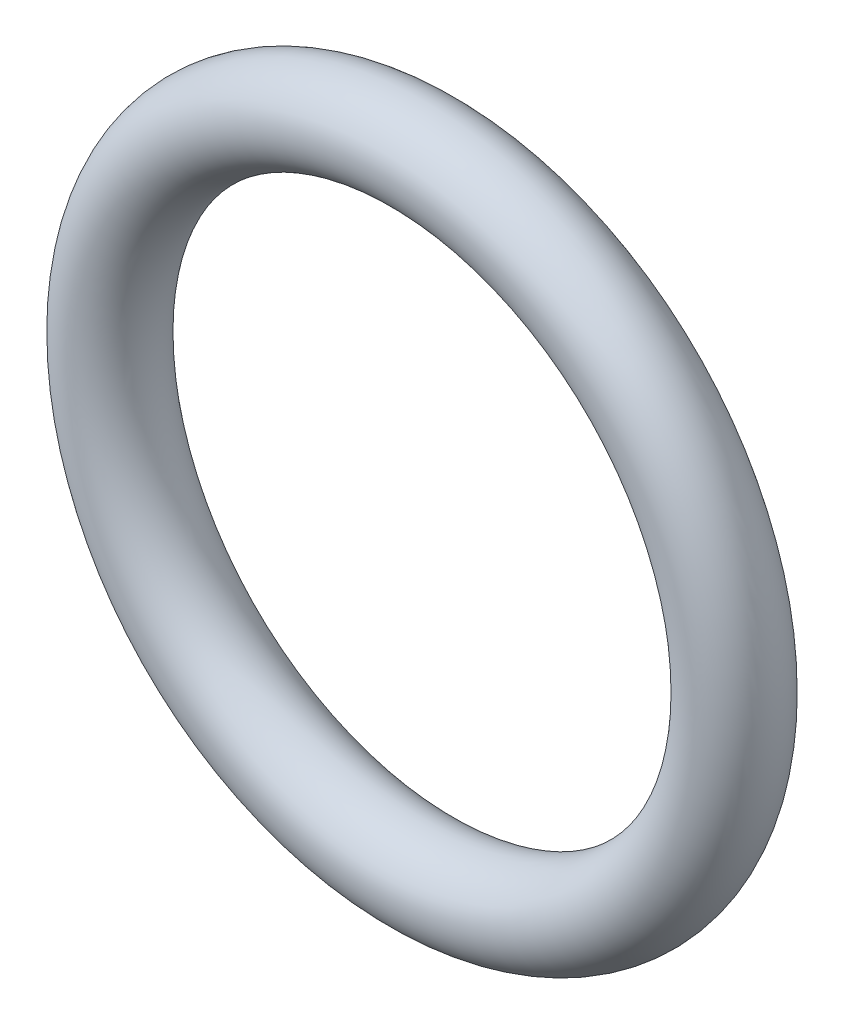
SolidWorks part; units mm, degrees
ref_plane "Спереди" through (0, 0, 0) normal (0, 0, 1) x (1, 0, 0)
ref_plane "Сверху" through (0, 0, 0) normal (0, 1, 0) x (1, 0, 0)
ref_plane "Справа" through (0, 0, 0) normal (1, 0, 0) x (0, 0, -1)
other "Configuration Table"
sketch "Эскиз1" plane through (0, 0, 0) normal (1, 0, 0) x (0, 0, -1)
  line L0 (-8.4104, 0) -> (13.8874, 0) construction
  line L1 (0, 0) -> (0, 8) construction
  circle A0 centre (0, 9.335) radius 1.335
  dimension "D2" = 2.67
  dimension "D1" = 8
revolve "Повернуть1" add sketch "Эскиз1" angle 360 about L0
ref_axis "Ось1" through (0, 0, -80.9) along (0, 0, 1)
